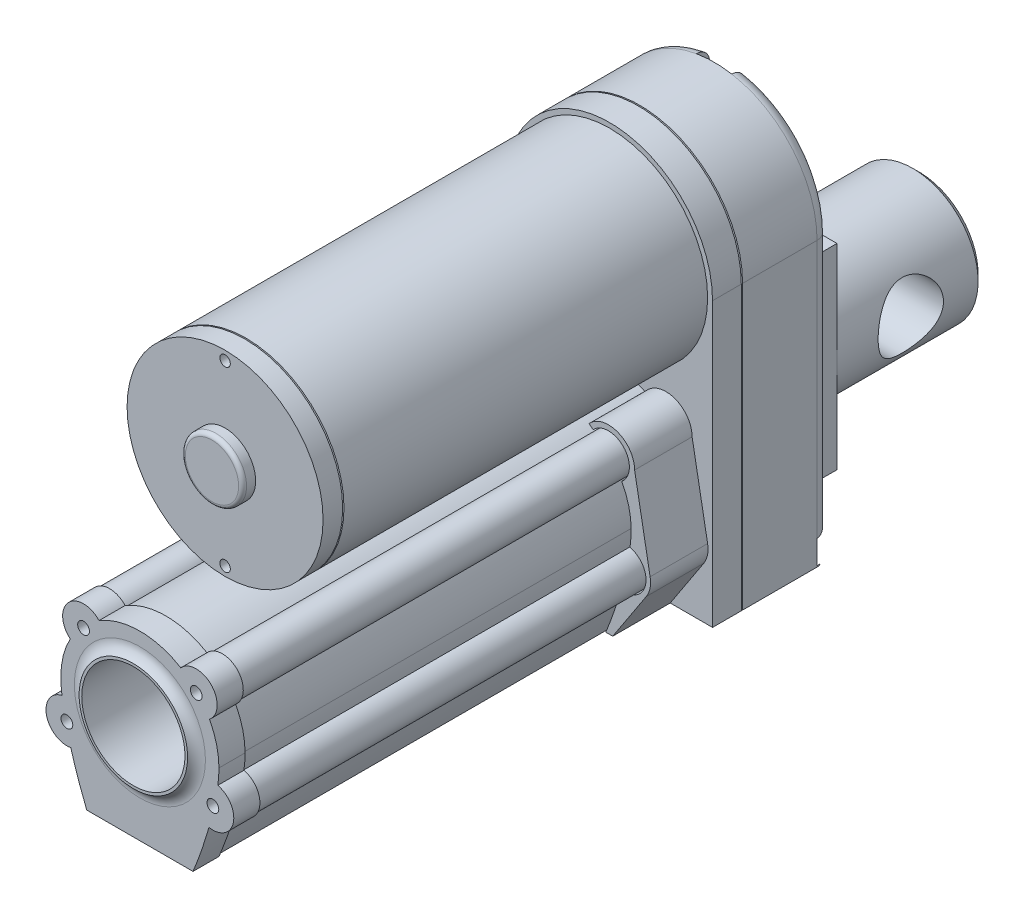
SolidWorks part; units mm, degrees
ref_plane "Front Plane" through (0, 0, 0) normal (0, 0, 1) x (1, 0, 0)
ref_plane "Top Plane" through (0, 0, 0) normal (0, 1, 0) x (1, 0, 0)
ref_plane "Right Plane" through (0, 0, 0) normal (1, 0, 0) x (0, 0, -1)
sketch "Sketch1" plane through (0, 0, 0) normal (0, 0, 1) x (1, 0, 0)
  line L0 (0, 0) -> (0, 55.0037)
  line L1 (0, 0) -> (40.005, 0)
  line L2 (40.005, 0) -> (40.005, 55.0037)
  arc A0 (40.005, 55.0037) -> (0, 55.0037) centre (20.0025, 55.0037) ccw
  dimension "D1" = 75.0062
  dimension "D2" = 40.005
extrude "Boss-Extrude1" add sketch "Sketch1" along normal mid plane 17.018 contours L0 A0 L2 L1
ref_plane "Plane1" through (0, 0, 8.763) normal (0, 0, 1) x (1, 0, 0)
sketch "Sketch5" plane through (0, 0, 8.763) normal (0, 0, 1) x (1, 0, 0)
  line L0 (0, 0) -> (0, 55.0037) construction
  line L1 (0, 0) -> (40.005, 0) construction
  line L2 (40.005, 0) -> (40.005, 55.0037) construction
  line L3 (0, 0) -> (0, 55.0037)
  line L4 (0, 0) -> (40.005, 0)
  line L5 (40.005, 0) -> (40.005, 55.0037)
  arc A0 (40.005, 55.0037) -> (0, 55.0037) centre (20.0025, 55.0037) ccw construction
  arc A1 (40.005, 55.0037) -> (0, 55.0037) centre (20.0025, 55.0037) ccw
extrude "Boss-Extrude3" add sketch "Sketch5" along normal blind 5.588 separate body
fillet "Fillet1" radius 2.54 4 edges at (40.005, 27.5018, -8.509) (0, 27.5018, -8.509) (20.0025, 0, -8.509) (20.0025, 75.0062, -8.509)
sketch "Sketch6" plane through (0, 0, 14.351) normal (0, 0, 1) x (1, 0, 0)
  circle A0 centre (20.0025, 55.0037) radius 19.05
  dimension "D1" = 38.1
extrude "Boss-Extrude4" add sketch "Sketch6" along normal blind 70.6882
sketch "Sketch9" plane through (0, 0, -8.509) normal (0, 0, -1) x (-1, 0, 0)
  line L0 (-16.5735, 71.628) -> (-16.5735, 75.184)
  line L1 (-23.4315, 71.628) -> (-23.4315, 75.184)
  line L2 (-23.4315, 75.184) -> (-16.5735, 75.184)
  line L3 (-37.465, 2.54) -> (-2.54, 2.54) construction
  line L5 (-20.0025, 2.54) -> (-20.0025, 140.716) construction
  circle A0 centre (-37.465, 2.54) radius 3.429
  circle A1 centre (-2.54, 2.54) radius 3.429
  arc A2 (-23.4315, 71.628) -> (-16.5735, 71.628) centre (-20.0025, 71.628) ccw
  dimension "D1" = 6.858
  dimension "D2" = 6.858
  dimension "D3" = 6.858
  dimension "D4" = 3.556
  dimension "D5" = 69.088
extrude "Cut-Extrude1" cut sketch "Sketch9" against normal blind 2.54
sketch "Sketch10" plane through (0, 0, 14.351) normal (0, 0, 1) x (1, 0, 0)
  line L0 (20.0025, -8.5483) -> (20.0025, 28.86) construction
  line L1 (9.8425, 0) -> (30.1625, 0)
  line L2 (0, 0) -> (40.005, 0) construction
  line L3 (0, 55.0037) -> (0, 0) construction
  circle A0 centre (20.0025, 19.685) radius 10.033
  arc A1 (35.1155, 19.685) -> (33.2111, 27.029) centre (20.0025, 19.685) ccw
  arc A2 (33.2556, 9.0067) -> (34.8711, 16.4489) centre (34.1913, 12.7) ccw
  arc A3 (33.2111, 27.029) -> (28.0023, 32.5071) centre (30.9547, 30.099) ccw
  arc A4 (6.7494, 9.0067) -> (5.1339, 16.4489) centre (5.8137, 12.7) cw
  arc A5 (6.7939, 27.029) -> (12.0027, 32.5071) centre (9.0503, 30.099) cw
  arc A6 (28.0023, 32.5071) -> (12.0027, 32.5071) centre (20.0025, 19.685) ccw
  arc A7 (6.7939, 27.029) -> (4.8895, 19.685) centre (20.0025, 19.685) ccw
  spline S0 degree 3 poles (30.1625, 0) (31.2263, 2.6097) (32.3487, 5.7927) (33.2556, 9.0067) knots 0 0 0 0 0.457098 0.457098 0.457098 0.457098
  spline S1 degree 3 poles (9.8425, 0) (8.7787, 2.6097) (7.6563, 5.7927) (6.7494, 9.0067) knots 0 0 0 0 0.457098 0.457098 0.457098 0.457098
  spline S2 degree 3 poles (5.1339, 16.4489) (4.9872, 17.5419) (4.8946, 18.6236) (4.8895, 19.6345) (4.8895, 19.685) knots 0.819985 0.819985 0.819985 0.819985 0.990999 1 1 1 1
  spline S3 degree 3 poles (34.8711, 16.4489) (35.0178, 17.5419) (35.1104, 18.6236) (35.1155, 19.6345) (35.1155, 19.685) knots 0.819985 0.819985 0.819985 0.819985 0.990999 1 1 1 1
  point P14 (20.0025, 0)
  dimension "D2" = 20.066
  dimension "D4" = 30.226
  dimension "D3" = 34.798
  dimension "D5" = 7.7096
  dimension "D9" = 7.62
  dimension "D10" = 34.1913
  dimension "D1" = 10.16
  dimension "D6" = 5.8489
  dimension "D7" = 12.7
  dimension "D8" = 30.099
  dimension "D11" = 5.1339
  dimension "D12" = 6.7494
  dimension "D13" = 32.2954
extrude "Boss-Extrude6" add sketch "Sketch10" along normal blind 86.233 contours A0 | A6 A5 A7 S2 A4 S1 L1 S0 A2 S3 A1 A3
sketch "Sketch12" plane through (0, 0, 100.584) normal (0, 0, 1) x (1, 0, 0)
  line L2 (9.6717, -0.254) -> (30.3333, -0.254)
  line L3 (9.6717, -0.254) -> (30.3333, -0.254)
  circle A7 centre (20.0025, 19.685) radius 10.033 construction
  circle A8 centre (20.0025, 19.685) radius 10.033
  arc A14 (33.5376, 26.9614) -> (27.9511, 32.8366) centre (30.9547, 30.099) ccw
  arc A15 (27.9511, 32.8366) -> (12.0539, 32.8366) centre (20.0025, 19.685) ccw
  arc A16 (12.0539, 32.8366) -> (6.4674, 26.9614) centre (9.0503, 30.099) ccw
  arc A17 (6.4674, 26.9614) -> (4.6355, 19.685) centre (20.0025, 19.685) ccw
  arc A18 (4.8516, 16.6485) -> (6.5704, 8.7071) centre (5.8137, 12.7) ccw
  arc A19 (33.4346, 8.7071) -> (35.1534, 16.6485) centre (34.1913, 12.7) ccw
  arc A20 (35.3695, 19.685) -> (33.5376, 26.9614) centre (20.0025, 19.685) ccw
  arc A21 (33.5376, 26.9614) -> (27.9511, 32.8366) centre (30.9547, 30.099) ccw
  arc A22 (27.9511, 32.8366) -> (12.0539, 32.8366) centre (20.0025, 19.685) ccw
  arc A23 (12.0539, 32.8366) -> (6.4674, 26.9614) centre (9.0503, 30.099) ccw
  arc A24 (6.4674, 26.9614) -> (4.6355, 19.685) centre (20.0025, 19.685) ccw
  arc A25 (4.8516, 16.6485) -> (6.5704, 8.7071) centre (5.8137, 12.7) ccw
  arc A26 (33.4346, 8.7071) -> (35.1534, 16.6485) centre (34.1913, 12.7) ccw
  arc A27 (35.3695, 19.685) -> (33.5376, 26.9614) centre (20.0025, 19.685) ccw
  spline S8 degree 3 poles (3001.0592, -87.1889) (-3016.0112, 306.3589) (3025.5743, -309.9621) (-2987.7512, 210.2659) knots -38.253728 -38.253728 -38.253728 -38.253728 41.995553 41.995553 41.995553 41.995553 only from (4.6355, 19.685) to (4.8516, 16.6485)
  spline S9 degree 3 poles (2942.8657, 550.3804) (134.5674, 290.2857) (-29.5411, 112.7018) (8.2588, 3.4372) (8.527, 2.6934) (37.4017, -74.0852) (188.1428, -103.8588) (-2695.5332, -1282.9861) knots -35.807014 -35.807014 -35.807014 -35.807014 0.5 0.5 0.75 0.75 26.443477 26.443477 26.443477 26.443477 only from (6.5704, 8.7071) to (9.6717, -0.254)
  spline S10 degree 3 poles (2721.4691, -1312.3327) (-147.2993, -102.4615) (2.6344, -74.0034) (31.4782, 2.6939) (31.7464, 3.4377) (69.6516, 113.0092) (-96.4312, 288.2244) (-2785.7874, 1000.652) knots -25.408422 -25.408422 -25.408422 -25.408422 0.25 0.25 0.5 0.5 36.909627 36.909627 36.909627 36.909627 only from (30.3333, -0.254) to (33.4346, 8.7071)
  spline S11 degree 3 poles (3029.4649, 182.1475) (-2986.9479, -283.6551) (3057.0444, 281.6839) (-2961.724, -64.0429) knots -41.009223 -41.009223 -41.009223 -41.009223 39.261525 39.261525 39.261525 39.261525 only from (35.1534, 16.6485) to (35.3695, 19.685)
  spline S12 degree 3 poles (4.6355, 19.685) (4.6355, 18.6694) (4.7231, 17.6558) (4.8516, 16.6485) knots 0 0 0 0 1 1 1 1
  spline S13 degree 3 poles (6.5704, 8.7071) (7.0045, 7.1864) (7.4833, 5.6789) (8.2588, 3.4372) (8.527, 2.6934) (9.0835, 1.2137) (9.3733, 0.4782) (9.6717, -0.254) knots 0 0 0 0 0.5 0.5 0.75 0.75 1 1 1 1
  spline S14 degree 3 poles (30.3333, -0.254) (30.6317, 0.4782) (30.9216, 1.2138) (31.4782, 2.6939) (31.7464, 3.4377) (32.5219, 5.6794) (33.0005, 7.1864) (33.4346, 8.7071) knots 0 0 0 0 0.25 0.25 0.5 0.5 1 1 1 1
  spline S15 degree 3 poles (35.1534, 16.6485) (35.2819, 17.6559) (35.3695, 18.6693) (35.3695, 19.685) knots 0 0 0 0 1 1 1 1
  dimension "D1" = 0.254
extrude "Boss-Extrude7" add sketch "Sketch12" along normal blind 5.08
sketch "Sketch14" plane through (0, 0, 105.664) normal (0, 0, 1) x (1, 0, 0)
  circle A0 centre (20.0025, 19.685) radius 10.033 construction
  circle A1 centre (20.0025, 19.685) radius 10.033
  circle A2 centre (20.0025, 19.685) radius 10.541
  dimension "D1" = 0.508
extrude "Boss-Extrude8" add sketch "Sketch14" along normal blind 1.27
fillet "Fillet2" radius 2.54 1 edges at (30.5435, 19.685, 105.664)
sketch "Sketch16" plane through (0, 0, -5.969) normal (0, 0, -1) x (-1, 0, 0)
  circle A0 centre (-37.465, 2.54) radius 1.143
  circle A1 centre (-2.54, 2.54) radius 1.143
  circle A2 centre (-20.0025, 71.628) radius 1.143
  dimension "D1" = 2.286
extrude "Cut-Extrude2" cut sketch "Sketch16" against normal blind 17.78
sketch "Sketch17" plane through (0, 0, 105.664) normal (0, 0, 1) x (1, 0, 0)
  circle A0 centre (30.9547, 30.099) radius 1.143
  circle A1 centre (34.1913, 12.7) radius 1.143
  circle A2 centre (5.8137, 12.7) radius 1.143
  circle A3 centre (9.0503, 30.099) radius 1.143
  dimension "D1" = 2.286
extrude "Cut-Extrude3" cut sketch "Sketch17" against normal blind 12.7
ref_plane "Plane3" through (0, 0, 85.2932) normal (0, 0, 1) x (1, 0, 0)
sketch "Sketch19" plane through (0, 0, 85.2932) normal (0, 0, 1) x (1, 0, 0)
  circle A0 centre (20.0025, 55.0037) radius 19.05 construction
  circle A1 centre (20.0025, 55.0037) radius 19.05
extrude "Boss-Extrude9" add sketch "Sketch19" along normal blind 3.81 separate body
sketch "Sketch20" plane through (0, 0, 89.1032) normal (0, 0, 1) x (1, 0, 0)
  circle A0 centre (20.0025, 55.0037) radius 5.9436
  dimension "D1" = 11.8872
extrude "Boss-Extrude10" add sketch "Sketch20" along normal blind 2.54
fillet "Fillet4" radius 0.762 1 edges at (25.9461, 55.0037, 91.6432)
ref_plane "Plane4" through (20.0025, 0, 0) normal (1, 0, 0) x (0, 0, -1)
sketch "Sketch24" plane through (0, 0, 89.1032) normal (0, 0, 1) x (1, 0, 0)
  line L0 (20.0025, 77.5374) -> (20.0025, 33.7577) construction
  line L1 (-2.5816, 55.0037) -> (44.7592, 55.0037) construction
  circle A0 centre (20.0025, 72.2757) radius 1.016
  circle A1 centre (20.0025, 37.7317) radius 1.016
  dimension "D1" = 2.032
  dimension "D2" = 17.272
extrude "Cut-Extrude6" cut sketch "Sketch24" against normal blind 12.7
sketch "Sketch25" plane through (0, 0, 14.351) normal (0, 0, 1) x (1, 0, 0)
  line L0 (30.1625, 0) -> (40.005, 0) construction
  line L1 (0, 0) -> (9.8425, 0) construction
  line L2 (30.4367, 0) -> (31.7791, 0)
  line L3 (8.2259, 0) -> (9.5683, 0)
  line L5 (0, 0) -> (9.8425, 0) construction
  line L6 (34.8708, 16.4453) -> (35.1155, 19.685) construction
  line L7 (36.2107, 17.3226) -> (36.3854, 19.6361) construction
  line L8 (36.0347, 30.099) -> (39.048, 13.6393)
  line L9 (38.2986, 9.938) -> (31.7791, 0)
  line L10 (5.1342, 16.4453) -> (4.8886, 19.6965) construction
  line L11 (3.7943, 17.3226) -> (3.6187, 19.6481) construction
  line L12 (20.0025, 23.731) -> (20.0025, -4.7422) construction
  line L13 (1.7064, 9.938) -> (8.2259, 0)
  line L14 (3.9703, 30.099) -> (0.957, 13.6393)
  line L15 (9.8425, 0) -> (6.752, 8.999) construction
  line L16 (8.0635, 1.27) -> (5.8742, 7.6451) construction
  line L17 (0, 1.27) -> (8.0635, 1.27) construction
  line L18 (30.824, 0) -> (40.005, 0) construction
  line L19 (32.4823, 1.27) -> (40.005, 1.27) construction
  line L20 (30.824, 0) -> (33.253, 8.999) construction
  line L21 (32.4823, 1.27) -> (34.2034, 7.6468) construction
  line L23 (12.0329, 32.8595) -> (12.8214, 33.5026)
  line L24 (27.9721, 32.8595) -> (27.1836, 33.5026)
  arc A6 (35.1418, 16.6513) -> (33.4346, 8.7071) centre (34.1913, 12.7) cw
  arc A12 (38.2986, 9.938) -> (39.048, 13.6393) centre (34.0511, 12.7245) ccw
  arc A13 (12.9869, 33.3098) -> (5.2238, 26.7576) centre (9.0503, 30.099) ccw construction
  arc A14 (36.0347, 30.099) -> (27.1836, 33.5026) centre (30.9547, 30.099) ccw
  arc A15 (12.8214, 33.5026) -> (3.9703, 30.099) centre (9.0503, 30.099) ccw
  arc A16 (3.7943, 17.3226) -> (5.8742, 7.6451) centre (5.9539, 12.7245) ccw construction
  arc A17 (0.957, 13.6393) -> (1.7064, 9.938) centre (5.9539, 12.7245) ccw
  arc A18 (36.3854, 19.6361) -> (34.7805, 26.7569) centre (20.0025, 19.685) ccw construction
  arc A19 (5.2238, 26.7576) -> (3.6187, 19.6481) centre (20.0025, 19.685) ccw construction
  arc A20 (34.2034, 7.6468) -> (36.2107, 17.3226) centre (34.0511, 12.7245) ccw construction
  arc A21 (34.7805, 26.7569) -> (27.0181, 33.3098) centre (30.9547, 30.099) ccw construction
  arc A22 (4.8639, 16.6514) -> (6.5704, 8.7071) centre (5.8137, 12.7) ccw
  arc A23 (6.4667, 26.9619) -> (4.6346, 19.687) centre (20.0025, 19.685) ccw
  arc A24 (12.0329, 32.8595) -> (6.4667, 26.9619) centre (9.0503, 30.099) ccw
  arc A26 (35.3695, 19.6754) -> (33.5376, 26.9614) centre (20.0025, 19.685) ccw
  arc A27 (33.5376, 26.9614) -> (27.9721, 32.8595) centre (30.9547, 30.099) ccw
  arc A28 (12.0027, 32.5071) -> (6.7932, 27.0295) centre (9.0503, 30.099) ccw construction
  arc A29 (6.7932, 27.0295) -> (4.8886, 19.6965) centre (20.0025, 19.685) ccw construction
  arc A30 (5.1342, 16.4453) -> (6.752, 8.999) centre (5.9539, 12.7245) ccw construction
  arc A31 (33.253, 8.999) -> (34.8708, 16.4453) centre (34.0511, 12.7245) ccw construction
  arc A32 (35.1155, 19.685) -> (33.2111, 27.029) centre (20.0025, 19.685) ccw construction
  arc A33 (33.2111, 27.029) -> (28.0023, 32.5071) centre (30.9547, 30.099) ccw construction
  spline S4 degree 3 poles (30.4367, 0) (30.5562, 0.2942) (30.8018, 0.9102) (31.3182, 2.2541) (31.9744, 4.0657) (32.736, 6.3526) (33.2106, 7.9226) (33.4346, 8.7071) knots 0.00546 0.00546 0.00546 0.00546 0.055775 0.111549 0.223098 0.334648 0.446197 0.446197 0.446197 0.446197
  spline S10 degree 3 poles (9.5683, 0) (9.4488, 0.2942) (9.2032, 0.9102) (8.6868, 2.2541) (8.0306, 4.0657) (7.269, 6.3526) (6.7944, 7.9226) (6.5704, 8.7071) knots 0.00546 0.00546 0.00546 0.00546 0.055775 0.111549 0.223098 0.334648 0.446197 0.446197 0.446197 0.446197
  spline S11 degree 3 poles (4.8639, 16.6514) (4.7954, 17.1705) (4.68, 18.2435) (4.6368, 19.1953) (4.6346, 19.687) knots 0.832123 0.832123 0.832123 0.832123 0.916061 1 1 1 1
  spline S15 degree 3 poles (35.1418, 16.6513) (35.2096, 17.1667) (35.3243, 18.2354) (35.3674, 19.1837) (35.3695, 19.6754) knots 0.832741 0.832741 0.832741 0.832741 0.916061 1 1 1 1
  dimension "D1" = 1.27
extrude "Boss-Extrude12" add sketch "Sketch25" along normal blind 11.176
sketch "Sketch26" plane through (0, 0, -8.509) normal (0, 0, -1) x (-1, 0, 0)
  line L1 (-32.7025, 45.2491) -> (-7.3025, 45.2491)
  line L2 (-32.7025, 45.2491) -> (-32.7025, 7.1491)
  line L3 (-32.7025, 7.1491) -> (-7.3025, 7.1491)
  line L4 (-7.3025, 45.2491) -> (-7.3025, 7.1491)
  line L5 (-32.7025, 45.2491) -> (-7.3025, 7.1491) construction
  line L6 (-32.7025, 7.1491) -> (-7.3025, 45.2491) construction
  point P0 (-20.0025, 26.1991)
  dimension "D1" = 38.1
  dimension "D2" = 25.4
extrude "Boss-Extrude13" add sketch "Sketch26" along normal blind 8.636
sketch "Sketch27" plane through (0, 0, -17.145) normal (0, 0, -1) x (-1, 0, 0)
  circle A0 centre (-20.0025, 25.13) radius 12.7
  dimension "D1" = 25.4
extrude "Boss-Extrude14" add sketch "Sketch27" along normal blind 28.702
ref_plane "Plane5" through (20.0025, 0, 0) normal (1, 0, 0) x (0, 0, -1)
sketch "Sketch28" plane through (20.0025, 0, 0) normal (1, 0, 0) x (0, 0, -1)
  circle A0 centre (31.496, 25.13) radius 6.35
  dimension "D1" = 12.7
extrude "Cut-Extrude7" cut sketch "Sketch28" against normal mid plane 28.702
chamfer "Chamfer1" distance 1.27 angle 45 1 edges at (7.3025, 25.13, -45.847)
